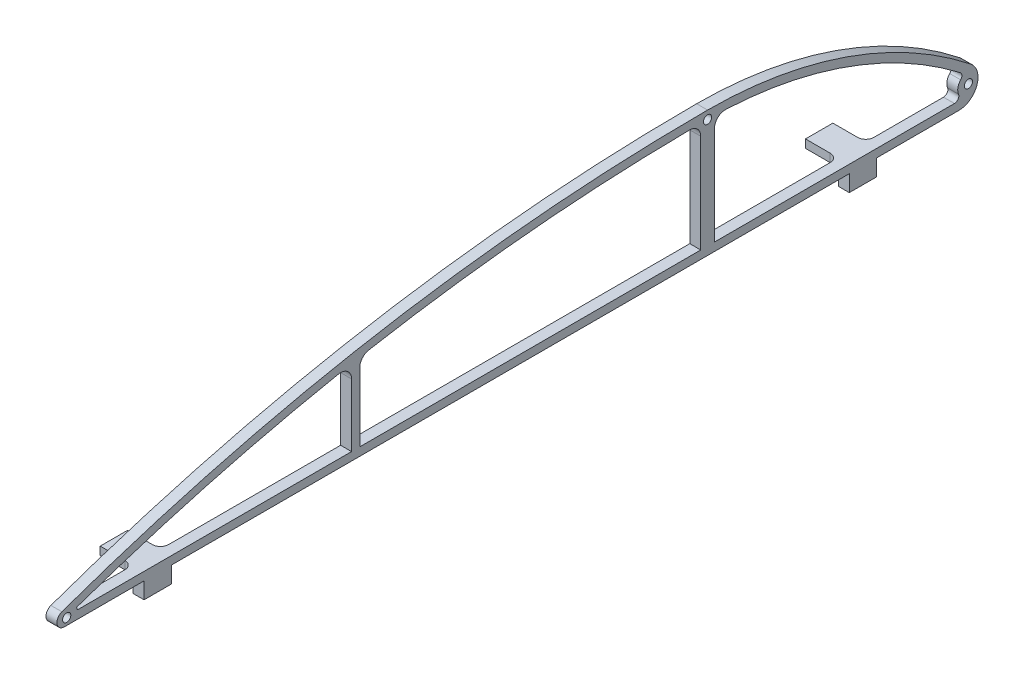
SolidWorks part; units mm, degrees
other "Marquage1"
sketch "Esquisse8" plane through (8, 0, -172.8424) normal (1, 0, 0) x (0, 0, -1)
other "Marquage2"
sketch "Esquisse10" plane through (-6, 20, -172.8424) normal (-0.8365, 0.2588, -0.483) x (-0.5, 0, 0.866)
other "Marquage3"
sketch "Esquisse11" plane through (0, 0, 0) normal (-0.0501, -0.1345, 0.9896) x (0.9942, 0.0873, 0.0622)
ref_plane "Plan de face" through (0, 0, 0) normal (0, 0, 1) x (1, 0, 0)
ref_plane "Plan de dessus" through (0, 0, 0) normal (0, 1, 0) x (1, 0, 0)
ref_plane "Plan de droite" through (0, 0, 0) normal (1, 0, 0) x (0, 0, -1)
sketch "Esquisse2" plane through (0, 0, 0) normal (1, 0, 0) x (0, 0, -1)
  line L0 (0, 0) -> (170.8732, 0)
  arc A1 (173.0499, 6.2408) -> (125, 23) centre (125, -54.2609) ccw
  arc A3 (170.8732, 0) -> (173.0499, 6.2408) centre (170.8732, 3.5) ccw
  arc A4 (125, 23) -> (0, 0) centre (125, -328.1739) ccw
  point P10 (180, 0)
  dimension "D1" = 180
  dimension "D2" = 3.5
  dimension "D3" = 23
  dimension "D4" = 55
extrude "Boss.-Extru.1" add sketch "Esquisse2" along normal blind 2
sketch "Esquisse4" plane through (2, 0, 0) normal (1, 0, 0) x (0, 0, -1)
  line L1 (0, 0) -> (8, 1.25) construction
  line L10 (174.369, 3.3283) -> (172.619, 3.3283) construction
  circle A6 centre (125, 21.5) radius 0.75
  circle A12 centre (172.619, 3.3283) radius 0.75
  arc A13 (170.8732, 0) -> (173.0499, 6.2408) centre (170.8732, 3.5) ccw construction
  circle A15 centre (8, 1.25) radius 0.75
  dimension "D1" = 1.5
  dimension "D2" = 1.5
  dimension "D7" = 1.5
  dimension "D3" = 1.5
  dimension "D4" = 8
  dimension "D5" = 1.25
  dimension "D6" = 1.75
extrude "Enlèv. mat.-Extru.2" cut sketch "Esquisse4" against normal through all
sketch "Esquisse9" plane through (0, 0, 0) normal (1, 0, 0) x (0, 0, -1)
  line L26 (126.25, 1.5) -> (171.941, 1.5)
  line L35 (8.4369, 1.5) -> (170.8732, 1.5)
  line L36 (9.9339, 1.5) -> (60, 1.5)
  line L40 (61.5, 1.5) -> (123.75, 1.5)
  line L42 (60, 1.5) -> (60, 15.4055)
  line L44 (61.5, 1.5) -> (61.5, 15.6859)
  line L45 (123.75, 21.4978) -> (123.75, 1.5)
  line L46 (126.25, 21.4978) -> (126.25, 1.5)
  arc A20 (60, 15.4055) -> (9.8076, 1.9814) centre (125, -328.1739) ccw
  circle A21 centre (125, 21.5) radius 0.75 construction
  circle A22 centre (8, 1.25) radius 0.75 construction
  arc A23 (173.0499, 6.2408) -> (125, 23) centre (125, -54.2609) ccw construction
  arc A25 (171.9926, 5.175) -> (171.941, 1.5) centre (172.619, 3.3283) ccw
  circle A26 centre (172.619, 3.3283) radius 0.75 construction
  arc A35 (170.8732, 1.5) -> (172.117, 5.0662) centre (170.8732, 3.5) ccw
  arc A39 (172.117, 5.0662) -> (125, 21.5) centre (125, -54.2609) ccw
  arc A40 (125, 21.5) -> (8.4369, 1.5) centre (125, -328.1739) ccw
  arc A42 (171.9926, 5.175) -> (126.25, 21.4978) centre (125, -54.2609) ccw
  arc A43 (123.75, 21.4978) -> (61.5, 15.6859) centre (125, -328.1739) ccw
  arc A54 (9.9339, 1.5) -> (9.8076, 1.9814) centre (8, 1.25) ccw
  dimension "D1" = 1.5
  dimension "D2" = 1.25
  dimension "D3" = 1.2
  dimension "D5" = 1.25
  dimension "D4" = 1.2
  dimension "D6" = 1.5
  dimension "D7" = 60
extrude "Enlèv. mat.-Extru.3" cut sketch "Esquisse9" along normal blind 4
fillet "Congé2" radius 1.35 1 edges at (1, 0, 0)
sketch "Esquisse12" plane through (0, 0, 0) normal (0, -1, 0) x (1, 0, 0)
  line L0 (0, -155.8732) -> (2, -155.8732)
  line L1 (0, -7.5659) -> (0, -170.8732) construction
  line L2 (2, -7.5659) -> (2, -170.8732) construction
  line L3 (2, -170.8732) -> (0, -170.8732) construction
  line L4 (0, -150.8732) -> (2, -150.8732)
  line L5 (0, -27.1127) -> (2, -27.1127)
  line L6 (0, -22.1127) -> (2, -22.1127)
  line L7 (0, -7.1127) -> (2, -7.1127) construction
  line M5 (2, -170.8732) -> (2, -7.5659)
  line M7 (0, -7.5659) -> (0, -170.8732)
  dimension "D1" = 15
  dimension "D2" = 5
  dimension "D3" = 15
  dimension "D4" = 5
extrude "Boss.-Extru.2" add sketch "Esquisse12" along normal blind 3 contours L4 L0 M7 M5 | L6 L5 M7 M5 region at (1, 0, -153.3732) region at (1, 0, -24.6127)
fillet "Congé3" radius 2 4 edges at (1, 21.4978, -126.25) (1, 21.4978, -123.75) (1, 15.4055, -60) (1, 15.6859, -61.5)
fillet "Congé4" radius 0.8 2 edges at (1, 1.5, -171.941) (1, 5.175, -171.9926)
sketch "Esquisse13" plane through (0, 0, 0) normal (-1, 0, 0) x (0, 0, 1)
  line L1 (-150.8732, -3) -> (-150.8732, 0) construction
  line L2 (-155.8732, 0) -> (-150.8732, 0)
  line L3 (-155.8732, 0) -> (-155.8732, 1.5)
  line L4 (-155.8732, 1.5) -> (-150.8732, 1.5)
  line L5 (-150.8732, 0) -> (-150.8732, 1.5)
  line L6 (-126.25, 1.5) -> (-170.0685, 1.5) construction
  line L7 (-22.1127, -3) -> (-22.1127, 0) construction
  line L8 (-27.1127, 0) -> (-22.1127, 0)
  line L9 (-27.1127, 0) -> (-27.1127, 1.5)
  line L10 (-27.1127, 1.5) -> (-22.1127, 1.5)
  line L11 (-22.1127, 0) -> (-22.1127, 1.5)
  line L12 (-9.9339, 1.5) -> (-60, 1.5) construction
extrude "Boss.-Extru.3" add sketch "Esquisse13" along normal blind 6
fillet "Congé5" radius 1.5 4 edges at (0, 0.75, -22.1127) (0, 0.75, -27.1127) (0, 0.75, -155.8732) (0, 0.75, -150.8732)
